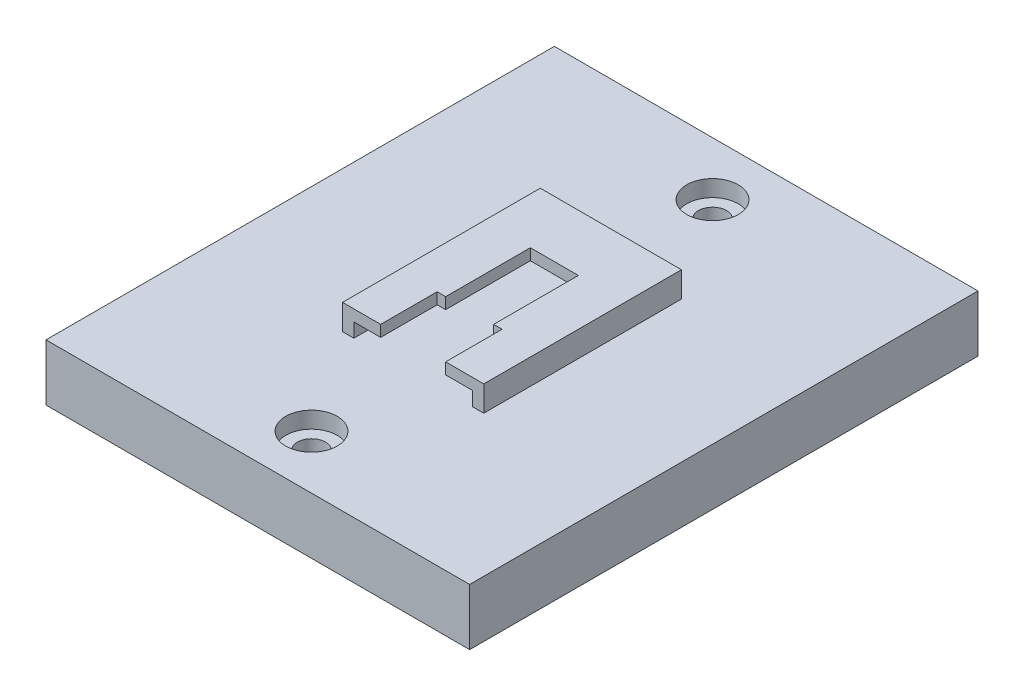
SolidWorks part; units mm, degrees
ref_plane "Front Plane" through (0, 0, 0) normal (0, 0, 1) x (1, 0, 0)
ref_plane "Top Plane" through (0, 0, 0) normal (0, 1, 0) x (1, 0, 0)
ref_plane "Right Plane" through (0, 0, 0) normal (1, 0, 0) x (0, 0, -1)
sketch "Sketch1" plane through (0, 0, 0) normal (0, 1, 0) x (1, 0, 0)
  line L0 (0, 23.0591) -> (0, -29.2863) construction
  line L1 (-12.5, 17.5) -> (12.5, 17.5)
  line L2 (-12.5, 17.5) -> (-12.5, -17.5)
  line L3 (-12.5, -17.5) -> (12.5, -17.5)
  line L4 (12.5, 17.5) -> (12.5, -17.5)
  line L5 (-12.5, 17.5) -> (12.5, -17.5) construction
  line L6 (-12.5, -17.5) -> (12.5, 17.5) construction
  line L7 (-5.75, -17.5) -> (5.75, -17.5)
  line L8 (-5.75, -17.5) -> (-5.75, -7.5)
  line L9 (-5.75, -7.5) -> (5.75, -7.5)
  line L10 (5.75, -17.5) -> (5.75, -7.5)
  line L11 (-4.25, -7.5) -> (4.25, -7.5)
  line L12 (-4.25, -7.5) -> (-4.25, 7.5)
  line L13 (-4.25, 7.5) -> (4.25, 7.5)
  line L14 (4.25, -7.5) -> (4.25, 7.5)
  point P0 (0, 0)
  dimension "D1" = 25
  dimension "D2" = 35
  dimension "D3" = 11.5
  dimension "D4" = 8.5
  dimension "D5" = 10
  dimension "D6" = 25
extrude "Boss-Extrude1" add sketch "Sketch1" along normal blind 2 contours L14 L9 L10 L3 L4 L1 L2 L8 L12 L13 region at (0, 0, -17.0699)
sketch "Sketch2" plane through (0, 0, 0) normal (0, -1, 0) x (1, 0, 0)
  line L0 (-12.5, 17.5) -> (-12.5, -17.5)
  line L1 (-12.5, -17.5) -> (12.5, -17.5)
  line L2 (12.5, -17.5) -> (12.5, 17.5)
  line L3 (12.5, 17.5) -> (10.5, 17.5)
  line L4 (5.75, 17.5) -> (12.5, 17.5) construction
  line L5 (10.5, 17.5) -> (10.5, -15.5)
  line L6 (10.5, -15.5) -> (-10.5, -15.5)
  line L7 (-10.5, -15.5) -> (-10.5, 17.5)
  line L8 (-12.5, 17.5) -> (-5.75, 17.5) construction
  line L9 (-10.5, 17.5) -> (-12.5, 17.5)
  dimension "D1" = 2
  dimension "D2" = 2
  dimension "D3" = 2
extrude "Boss-Extrude2" add sketch "Sketch2" along normal blind 2.5
sketch "Sketch3" plane through (0, -2.5, 0) normal (0, -1, 0) x (1, 0, 0)
  line L1 (-37.5, 45) -> (37.5, 45)
  line L2 (-37.5, 45) -> (-37.5, -45)
  line L3 (-37.5, -45) -> (37.5, -45)
  line L4 (37.5, 45) -> (37.5, -45)
  line L5 (-37.5, 45) -> (37.5, -45) construction
  line L6 (-37.5, -45) -> (37.5, 45) construction
  point P0 (0, 0)
  dimension "D1" = 75
  dimension "D2" = 90
extrude "Boss-Extrude3" add sketch "Sketch3" along normal blind 10
sketch "Sketch4" plane through (0, -2.5, 0) normal (0, 1, 0) x (1, 0, 0)
  line L0 (0, 52.8403) -> (0, -58.1898) construction
  line L1 (-26, 26) -> (26, 26) construction
  line L2 (-26, 26) -> (-26, -26) construction
  line L3 (-26, -26) -> (26, -26) construction
  line L4 (26, 26) -> (26, -26) construction
  line L5 (-26, 26) -> (26, -26) construction
  line L6 (-26, -26) -> (26, 26) construction
  line L7 (-11.2462, 35.5) -> (11.9137, 35.5) construction
  line L10 (-37.5, 45) -> (37.5, 45) construction
  line L11 (-55, 0) -> (55, 0) construction
  line L12 (-11.2462, -35.5) -> (11.9137, -35.5) construction
  point P0 (0, 0)
  dimension "D1" = 52
  dimension "D2" = 52
  dimension "D3" = 9.5
hole_wizard "CBORE for #8 Pan Head Machine Screw1" positions "Sketch5" profile "Sketch6" counterbore size "#8" standard "ANSI Inch" end condition through all
sketch "Sketch5" plane through (0, -2.5, 0) normal (0, 1, 0) x (1, 0, 0)
  line L0 (0, 52.8403) -> (0, -58.1898) construction
  line L1 (-11.2462, 35.5) -> (11.9137, 35.5) construction
  line L2 (-11.2462, -35.5) -> (11.9137, -35.5) construction
  point P0 (0, 35.5)
  point P6 (0, -35.5)
sketch "Sketch6" plane through (0, -2.5, -35.5) normal (1, 0, 0) x (0, 0, 1)
  line L0 (0, 0) -> (0, 10)
  line L1 (0, 10) -> (2.4892, 10)
  line L3 (2.4892, 10) -> (2.4892, 2.921)
  line L4 (2.4892, 2.921) -> (4.5644, 2.921)
  line L5 (4.5644, 2.921) -> (4.5644, 0)
  line L7 (4.5644, 0) -> (0, 0)
  line L11 (0, -6.35) -> (0, 107.95) construction
  dimension "Thru Hole Dia." = 4.9784
  dimension "Thru Hole Depth" = 10
  dimension "C'Bore Dia." = 9.1288
  dimension "C'Bore Depth" = 2.921
